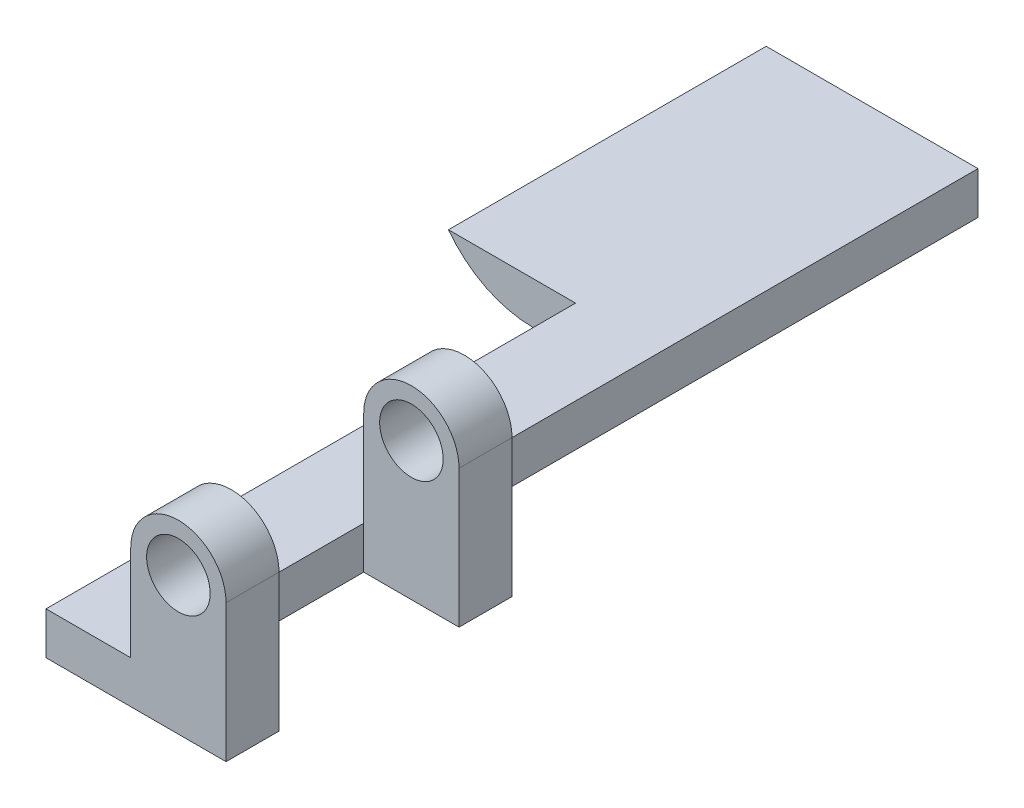
SolidWorks part; units mm, degrees
material "ABS"
ref_plane "Front Plane" through (0, 0, 0) normal (0, 0, 1) x (1, 0, 0)
ref_plane "Top Plane" through (0, 0, 0) normal (0, 1, 0) x (1, 0, 0)
ref_plane "Right Plane" through (0, 0, 0) normal (1, 0, 0) x (0, 0, -1)
sketch "Sketch1" plane through (0, 0, 0) normal (0, 0, 1) x (1, 0, 0)
  line L0 (33.6296, 23.9021) -> (41.6296, 23.9021)
  line L1 (41.6296, 23.9021) -> (41.6296, 19.9021)
  line L3 (41.6296, 23.9021) -> (41.6296, 32.9021)
  line L4 (41.6296, 19.9021) -> (50.6296, 19.9021)
  line L5 (50.6296, 19.9021) -> (50.6296, 32.9021)
  line L6 (41.6296, 32.9021) -> (41.6296, 23.9021)
  line L7 (41.6296, 19.9021) -> (33.6296, 19.9021)
  line L8 (33.6296, 19.9021) -> (33.6296, 23.9021)
  arc A1 (41.6296, 32.9021) -> (50.6296, 32.9021) centre (46.1296, 32.9021) cw
  circle A2 centre (46.1296, 32.9021) radius 3
  dimension "D3" = 6
  dimension "D4" = 4.5
  dimension "D1" = 4
  dimension "D2" = 8
  dimension "D5" = 13
extrude "Boss-Extrude1" add sketch "Sketch1" along normal blind 37 contours L8 L1 L0 | A1 L3 L1 L4 L5 A2 region at (37.6296, 21.9021, 0) region at (46.1296, 27.0967, 0)
sketch "Sketch3" plane through (0, 0, 0) normal (0, 0, -1) x (-1, 0, 0)
  line L1 (-33.6296, 19.9021) -> (-41.6296, 19.9021)
  line L2 (-33.6296, 19.9021) -> (-33.6296, 23.9021)
  line L3 (-33.6296, 23.9021) -> (-41.6296, 23.9021)
  line L4 (-41.6296, 19.9021) -> (-41.6296, 23.9021)
extrude "Boss-Extrude2" add sketch "Sketch3" along normal blind 13
sketch "Sketch4" plane through (0, 0, -13) normal (0, 0, -1) x (-1, 0, 0)
  line L0 (-41.6296, 19.9021) -> (-41.6296, 23.9021)
  line L5 (-41.6296, 19.9021) -> (-21.6296, 19.9021)
  line L6 (-41.6296, 23.9021) -> (-21.6296, 23.9021)
  line L7 (-21.6296, 19.9021) -> (-21.6296, 23.9021)
  dimension "D1" = 20
extrude "Boss-Extrude3" add sketch "Sketch4" along normal blind 30
fillet "Fillet1" radius 10 1 edges at (21.6296, 19.9021, -28)
sketch "Sketch5" plane through (0, 19.9021, 0) normal (0, -1, 0) x (-1, 0, 0)
  line L0 (-50.6296, -37) -> (-50.6296, 0) construction
  line L1 (-41.6296, 0) -> (-50.6296, 0)
  line L2 (-41.6296, 0) -> (-41.6296, -10)
  line L3 (-41.6296, -10) -> (-50.6296, -10)
  line L4 (-50.6296, 0) -> (-50.6296, -10)
  line L6 (-41.6296, -15) -> (-50.6296, -15)
  line L7 (-41.6296, -15) -> (-41.6296, -32)
  line L8 (-41.6296, -32) -> (-50.6296, -32)
  line L9 (-50.6296, -15) -> (-50.6296, -32)
  dimension "D1" = 17
  dimension "D2" = 5
  dimension "D3" = 10
extrude "Cut-Extrude1" cut sketch "Sketch5" against normal blind 19
